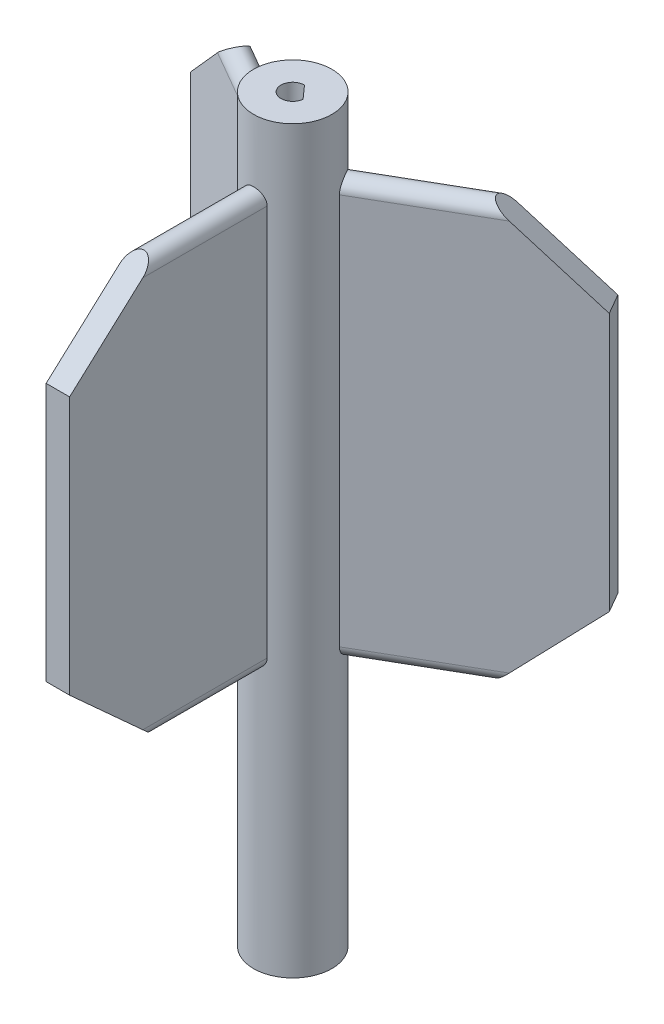
SolidWorks part; units mm, degrees
material "Rubber"
ref_plane "Front Plane" through (0, 0, 0) normal (0, 0, 1) x (1, 0, 0)
ref_plane "Top Plane" through (0, 0, 0) normal (0, 1, 0) x (1, 0, 0)
ref_plane "Right Plane" through (0, 0, 0) normal (1, 0, 0) x (0, 0, -1)
sketch "Sketch2" plane through (0, 0, 0) normal (0, 1, 0) x (1, 0, 0)
  circle A0 centre (0, 0) radius 5
  dimension "D1" = 10
extrude "Boss-Extrude1" add sketch "Sketch2" along normal blind 94.5
sketch "Sketch3" plane through (0, 0, 0) normal (0, 0, 1) x (1, 0, 0)
  line L0 (0, 85) -> (0, 35) construction
  line L1 (1.5, 85) -> (1.5, 35)
  line L2 (-1.5, 85) -> (-1.5, 35)
  arc A0 (1.5, 85) -> (-1.5, 85) centre (0, 85) ccw
  arc A1 (-1.5, 35) -> (1.5, 35) centre (0, 35) ccw
  point P3 (0, 60)
  dimension "D3" = 1.5
  dimension "D1" = 50
  dimension "D2" = 35
extrude "Boss-Extrude2" add sketch "Sketch3" along normal blind 30
sketch "Sketch12" plane through (-1.5, 0, 0) normal (-1, 0, 0) x (0, 0, 1)
  line L1 (30, 86.5) -> (30, 76.5)
  line L2 (30, 85) -> (30, 35) construction
  line L3 (30, 33.5) -> (19, 33.5)
  line L5 (19, 86.5) -> (30, 86.5)
  line L6 (30, 76.5) -> (19, 86.5)
  line L9 (30, 33.5) -> (30, 43.5)
  line L10 (30, 43.5) -> (19, 33.5)
  dimension "D1" = 10
  dimension "D2" = 11
  dimension "D3" = 10
  dimension "D4" = 11
ref_axis "Axis1" through (0, 94.5, 0) along (0, -1, 0)
extrude "Cut-Extrude5" cut sketch "Sketch12" against normal up to next
sketch "Sketch6" plane through (0, 94.5, 0) normal (0, 1, 0) x (1, 0, 0)
  line L0 (0, 1.5) -> (1.49, -0.1725)
  arc A0 (0, 1.5) -> (1.49, -0.1725) centre (0, 0) ccw
  circle A1 centre (0, 0) radius 5 construction
  dimension "D1" = 1.5
  dimension "D3" = 1.49
  dimension "D2" = 2.24
extrude "Cut-Extrude1" cut sketch "Sketch6" against normal blind 30
sketch "Sketch7" plane through (0, 0, 0) normal (0, 0, 1) x (1, 0, 0)
  circle A0 centre (0, 88.8591) radius 2
  dimension "D1" = 5.6409
  dimension "D2" = 4
extrude "Cut-Extrude2" cut sketch "Sketch7" against normal blind 10
pattern_circular "CirPattern1" count 3 over 360 about axis through (0, 94.5, 0) along (0, -1, 0) of "Boss-Extrude2"
sketch "Sketch13" plane through (0.75, 0, 1.299) normal (0.5, 0, 0.866) x (0.866, 0, -0.5)
  line L1 (30, 86.5) -> (30, 76.5)
  line L3 (30, 33.5) -> (19, 33.5)
  line L5 (19, 86.5) -> (30, 86.5)
  line L6 (30, 76.5) -> (19, 86.5)
  line L9 (30, 33.5) -> (30, 43.5)
  line L10 (30, 43.5) -> (19, 33.5)
  line L12 (30, 85) -> (30, 35) construction
  point P0 (0, 0)
  dimension "D1" = 10
  dimension "D2" = 11
  dimension "D3" = 10
  dimension "D4" = 11
sketch "Sketch14" plane through (0.75, 0, -1.299) normal (0.5, 0, -0.866) x (-0.866, 0, -0.5)
  line L1 (30, 86.5) -> (30, 76.5)
  line L3 (30, 33.5) -> (19, 33.5)
  line L5 (19, 86.5) -> (30, 86.5)
  line L6 (30, 76.5) -> (19, 86.5)
  line L8 (30, 85) -> (30, 35) construction
  line L9 (30, 33.5) -> (30, 43.5)
  line L10 (30, 43.5) -> (19, 33.5)
  point P0 (0, 0)
  dimension "D1" = 10
  dimension "D2" = 11
  dimension "D3" = 10
  dimension "D4" = 11
extrude "Cut-Extrude6" cut sketch "Sketch13" against normal up to next
extrude "Cut-Extrude7" cut sketch "Sketch14" against normal up to next
